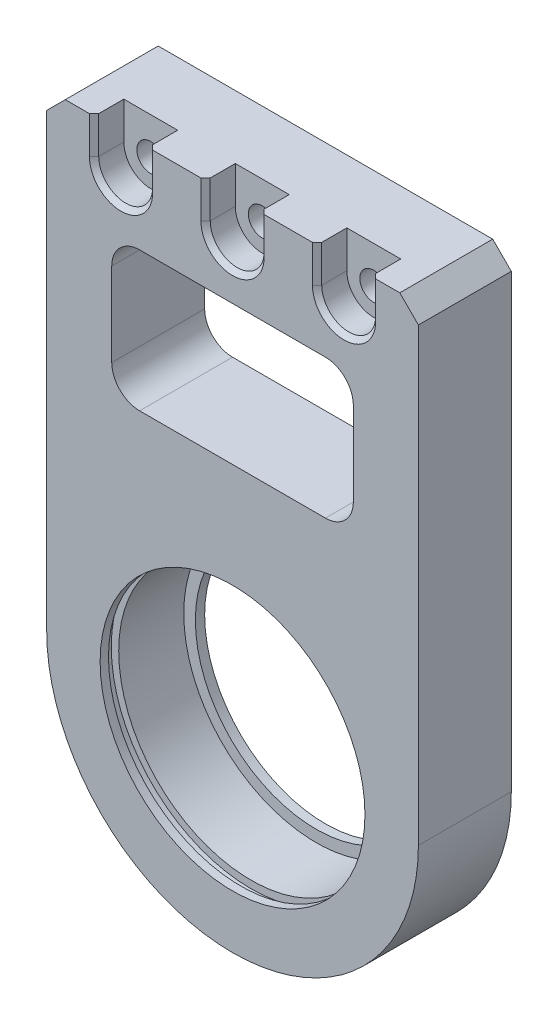
SolidWorks part; units mm, degrees
ref_plane "前视基准面" through (0, 0, 0) normal (0, 0, 1) x (1, 0, 0)
ref_plane "上视基准面" through (0, 0, 0) normal (0, 1, 0) x (1, 0, 0)
ref_plane "右视基准面" through (0, 0, 0) normal (1, 0, 0) x (0, 0, -1)
other "Configuration Table"
sketch "草图1" plane through (0, 0, 0) normal (0, 0, 1) x (1, 0, 0)
  line L1 (0, 0.5) -> (40, 0.5)
  line L2 (0, 0.5) -> (0, -70)
  line L3 (0, -70) -> (40, -70)
  line L4 (40, 0.5) -> (40, -70)
  dimension "D1" = 40
  dimension "D2" = 70.5
extrude "凸台-拉伸1" add sketch "草图1" along normal blind 10
sketch "草图2" plane through (0, 0, 10) normal (0, 0, 1) x (1, 0, 0)
  line L0 (0, -70) -> (40, -70) construction
  line L2 (0, 0.5) -> (0, -70) construction
  circle A0 centre (20, -50) radius 14.25
  dimension "D1" = 28.5
  dimension "D2" = 20
  dimension "D3" = 20
extrude "切除-拉伸1" cut sketch "草图2" against normal blind 12
ref_plane "基准面1" through (0, 0, 8) normal (0, 0, -1) x (-1, 0, 0)
sketch "草图3" plane through (0, 0, 8) normal (0, 0, -1) x (-1, 0, 0)
  circle A0 centre (-20, -50) radius 15.05
  dimension "D1" = 30.1
extrude "切除-拉伸2" cut sketch "草图3" against normal blind 1.1
chamfer "倒角1" distance 2 angle 45 2 edges at (40, 0.5, 5) (0, 0.5, 5)
fillet "圆角1" radius 20 2 edges at (0, -70, 5) (40, -70, 5)
sketch "草图4" plane through (0, 0, 0) normal (0, 0, -1) x (-1, 0, 0)
  line L0 (-40, -50) -> (-40, -1.5) construction
  line L1 (-38, 0.5) -> (-2, 0.5) construction
  circle A0 centre (-32, -3.5) radius 1.5
  circle A1 centre (-20, -3.5) radius 1.5
  circle A2 centre (-8, -3.5) radius 1.5
  dimension "D1" = 3
  dimension "D2" = 8
  dimension "D3" = 4
  dimension "D6" = 12
  dimension "D7" = 12
  dimension "D4" = 2
  dimension "D5" = 2
extrude "切除-拉伸3" cut sketch "草图4" against normal blind 15
sketch "草图5" plane through (0, 0, 0) normal (0, 0, -1) x (-1, 0, 0)
  line L0 (-40, -50) -> (-40, -1.5) construction
  line L1 (-33, -9.5) -> (-7, -9.5)
  line L2 (-33, -9.5) -> (-33, -24.5)
  line L3 (-33, -24.5) -> (-7, -24.5)
  line L4 (-7, -9.5) -> (-7, -24.5)
  line L5 (-33, -9.5) -> (-7, -24.5) construction
  line L6 (-33, -24.5) -> (-7, -9.5) construction
  line L7 (-38, 0.5) -> (-2, 0.5) construction
  point P0 (-20, -17)
  dimension "D1" = 26
  dimension "D2" = 15
  dimension "D3" = 7
  dimension "D4" = 10
extrude "切除-拉伸4" cut sketch "草图5" against normal blind 15
fillet "圆角2" radius 3 4 edges at (7, -24.5, 5) (7, -9.5, 5) (33, -24.5, 5) (33, -9.5, 5)
sketch "草图7" plane through (0, 0, 0) normal (0, 0, -1) x (-1, 0, 0)
  circle A0 centre (-20, -50) radius 14.25
  circle A1 centre (-20, -50) radius 14.25 construction
  circle A2 centre (-20, -50) radius 13
  dimension "D1" = 28.5
  dimension "D2" = 0
  dimension "D3" = 26
extrude "凸台-拉伸2" add sketch "草图7" against normal blind 1
sketch "草图8" plane through (0, 0, 10) normal (0, 0, 1) x (1, 0, 0)
  line L0 (38, 0.5) -> (2, 0.5) construction
  line L2 (5.1, -3.5) -> (5.1, 0.5)
  line L3 (5.1, 0.5) -> (10.9, 0.5)
  line L4 (10.9, -3.5) -> (10.9, 0.5)
  line L5 (17.1, -3.5) -> (17.1, 0.5)
  line L6 (22.9, -3.5) -> (22.9, 0.5)
  line L7 (34.9, -3.5) -> (34.9, 0.5)
  line L8 (29.1, 0.5) -> (34.9, 0.5)
  line L9 (29.1, -3.5) -> (29.1, 0.5)
  line L10 (17.1, 0.5) -> (22.9, 0.5)
  arc A0 (5.1, -3.5) -> (10.9, -3.5) centre (8, -3.5) ccw
  arc A2 (17.1, -3.5) -> (22.9, -3.5) centre (20, -3.5) ccw
  arc A3 (29.1, -3.5) -> (34.9, -3.5) centre (32, -3.5) ccw
  dimension "D1" = 5.8
  dimension "D2" = 5.8
  dimension "D3" = 2
  dimension "D5" = 12
  dimension "D4" = 2
extrude "切除-拉伸5" cut sketch "草图8" against normal blind 3.2
chamfer "倒角2" distance 0.5 angle 45 9 edges at (34.9, -1.5, 10) (32, -6.4, 10) (29.1, -1.5, 10) (22.9, -1.5, 10) (20, -6.4, 10) (17.1, -1.5, 10) (10.9, -1.5, 10) (8, -6.4, 10) (5.1, -1.5, 10)
